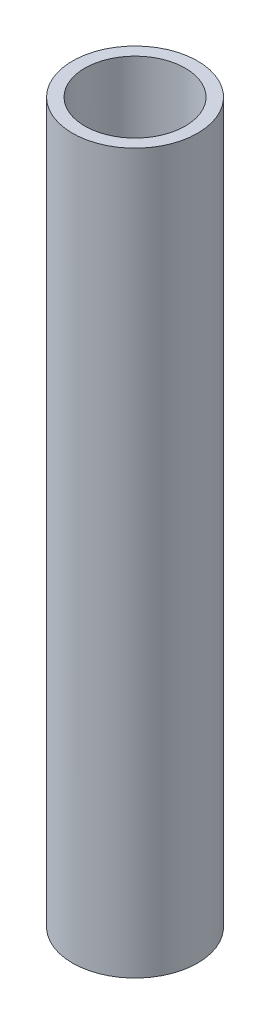
SolidWorks part; units mm, degrees
ref_plane "Front Plane" through (0, 0, 0) normal (0, 0, 1) x (1, 0, 0)
ref_plane "Top Plane" through (0, 0, 0) normal (0, 1, 0) x (1, 0, 0)
ref_plane "Right Plane" through (0, 0, 0) normal (1, 0, 0) x (0, 0, -1)
sketch "Sketch1" plane through (0, 0, 0) normal (0, 1, 0) x (1, 0, 0)
  circle A0 centre (0, 0) radius 4.05
  circle A1 centre (0, 0) radius 3.25
  dimension "D1" = 6.5
  dimension "D2" = 0.8
sketch "Sketch2" plane through (0, 0, 0) normal (0, 1, 0) x (1, 0, 0)
  circle A0 centre (0, 0) radius 3.25 construction
  circle A1 centre (0, 0) radius 4.05 construction
  circle A2 centre (0, 0) radius 3.25
  circle A3 centre (0, 0) radius 4.05
extrude "Boss-Extrude1" add sketch "Sketch2" along normal up to surface (46.5 mm away)
